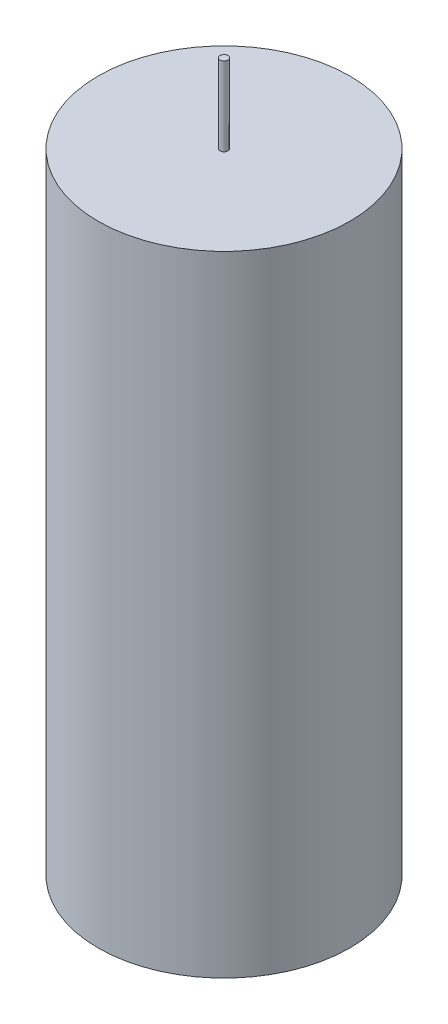
SolidWorks part; units mm, degrees
ref_plane "Alzado" through (0, 0, 0) normal (0, 0, 1) x (1, 0, 0)
ref_plane "Planta" through (0, 0, 0) normal (0, 1, 0) x (1, 0, 0)
ref_plane "Vista lateral" through (0, 0, 0) normal (1, 0, 0) x (0, 0, -1)
sketch "Croquis1" plane through (0, 0, 0) normal (0, 0, 1) x (1, 0, 0)
  line L0 (0, 250) -> (2.5, 250)
  line L1 (2.5, 250) -> (2.5, 200)
  line L2 (2.5, 200) -> (80, 200)
  line L3 (80, 200) -> (80, -200)
  line L4 (80, 0) -> (0, 0)
  line L5 (0, -250) -> (0, 250)
  line L6 (337.5089, 0) -> (-200.3399, 0) construction
  line L7 (0, 415.2531) -> (0, -321.1925) construction
  line L8 (2.5, -200) -> (80, -200)
  line L9 (2.5, -250) -> (2.5, -200)
  line L10 (0, -250) -> (2.5, -250)
  dimension "D1" = 80
  dimension "D2" = 2.5
  dimension "D3" = 200
  dimension "D4" = 250
revolve "Revolución1" add sketch "Croquis1" angle 360 about L7 region at (39.6996, 100.969, 0) region at (39.6996, -100.969, 0)
